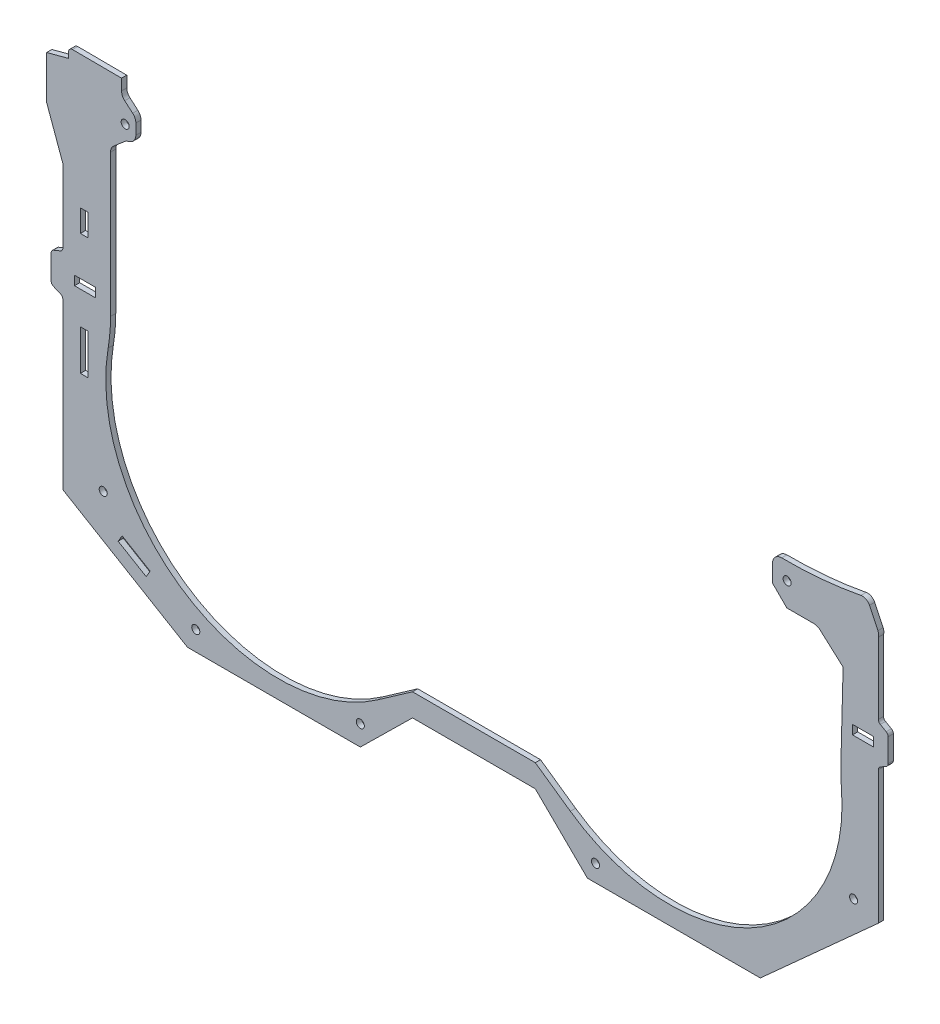
SolidWorks part; units mm, degrees
material "PPS"
ref_plane "前视基准面" through (0, 0, 0) normal (0, 0, 1) x (1, 0, 0)
ref_plane "上视基准面" through (0, 0, 0) normal (0, 1, 0) x (1, 0, 0)
ref_plane "右视基准面" through (0, 0, 0) normal (1, 0, 0) x (0, 0, -1)
sketch "草图1" plane through (0, 0, 0) normal (0, 0, 1) x (1, 0, 0)
  line L0 (-816.4831, 0) -> (39952.7477, 0) construction
  line L1 (0, 10.8762) -> (0, -592.6628) construction
  line L2 (0, 0) -> (206.9686, -284.8678) construction
  line L9 (155.1848, -135.6229) -> (109.8918, -176.4655)
  line L10 (109.8918, -176.4655) -> (43.5772, -176.4655)
  line L60 (-109.8918, -176.4655) -> (-43.5772, -176.4655)
  line L119 (-133.4625, -19.9819) -> (-139.4195, -25.1039)
  line L187 (152.75, -77.5) -> (145.75, -77.5) construction
  line L188 (152.75, -77.5) -> (152.75, -75) construction
  line L189 (145.75, -77.5) -> (145.75, -75) construction
  line L190 (152.75, -75) -> (145.75, -75) construction
  line L191 (-145.75, -75) -> (-152.75, -75) construction
  line L192 (-152.75, -75) -> (-152.75, -77.5) construction
  line L193 (-152.75, -77.5) -> (-145.75, -77.5) construction
  line L194 (-145.75, -77.5) -> (-145.75, -75) construction
  line L195 (145.25, -74.5) -> (153.25, -74.5)
  line L196 (153.25, -74.5) -> (153.25, -78)
  line L197 (153.25, -78) -> (145.25, -78)
  line L198 (145.25, -78) -> (145.25, -74.5)
  line L199 (-153.25, -78) -> (-145.25, -78)
  line L200 (-153.25, -74.5) -> (-153.25, -78)
  line L201 (-145.25, -74.5) -> (-153.25, -74.5)
  line L202 (-145.25, -78) -> (-145.25, -74.5)
  line L204 (-135.1929, 0) -> (-155.5041, 0.108)
  line L205 (-155.5041, 3.8169) -> (-155.5041, -3.6009) construction
  line L206 (-155.5041, 0.108) -> (-155.5041, -3.6009)
  line L207 (-155.5041, -3.6009) -> (-163.9299, -5.8429)
  line L208 (-155.5041, -3.6009) -> (-170.0041, -7.4592) construction
  line L209 (-163.9299, -5.8429) -> (-163.9299, -22.4613)
  line L210 (-163.9299, -22.4613) -> (-157.7253, -39.5836)
  line L211 (-157.7253, -39.5836) -> (-157.7253, -148.0115)
  line L212 (-157.7253, -148.0115) -> (-109.8918, -176.4655)
  line L215 (114.5778, -32.685) -> (114.5778, -42.9165)
  line L216 (120.0778, -48.4165) -> (131.782, -48.4165)
  line L217 (131.782, -48.4165) -> (141.6604, -57.2625)
  line L219 (151.7709, -31.6811) -> (155.0114, -38.4796)
  line L220 (155.1848, -40.6053) -> (155.1848, -135.6229)
  line L221 (120.1823, -39.335) -> (149.4323, -39.335) construction
  line L222 (96.3769, -48.4165) -> (142.5788, -48.4165) construction
  line L223 (75, -103.2286) -> (164.6276, -103.2286) construction
  line L224 (75, -103.2286) -> (37.0006, -157.4975) construction
  line L226 (37.0006, -157.4975) -> (23.5599, -148.0862)
  line L227 (23.5599, -148.0862) -> (-23.5599, -148.0862)
  line L228 (23.5599, -156.7643) -> (-23.5599, -156.7643)
  line L229 (23.5599, -156.7643) -> (43.5772, -176.4655)
  line L230 (-37.0006, -157.4975) -> (-23.5599, -148.0862)
  line L231 (-23.5599, -156.7643) -> (-43.5772, -176.4655)
  line L233 (114.5778, -42.9165) -> (120.0778, -48.4165)
  line L234 (75, -103.2286) -> (140.6832, -94.5813) construction
  line L235 (141.6604, -57.2625) -> (140.6832, -94.5813)
  line L236 (140.6832, -94.5813) -> (140.6832, -61.0285) construction
  line L238 (-139.4195, -87.7629) -> (-75, -103.2286) construction
  line L239 (-75, -103.2286) -> (-141.25, -103.2286) construction
  line L240 (-139.4195, -25.1039) -> (-139.4195, -87.7629)
  line L241 (-135.1929, 0) -> (-135.1929, -5.85)
  line L242 (-135.1929, -5.85) -> (-129.7197, -10.5767)
  line L243 (-129.7197, -10.5767) -> (-129.7197, -18.7984)
  line L244 (-129.7197, -18.7984) -> (-133.4625, -19.9819)
  circle A76 centre (75, -103.2286) radius 66.25 construction
  circle A78 centre (-133.8062, -14.6009) radius 1.55
  arc A79 (155.0114, -38.4796) -> (155.1848, -40.6053) centre (152.3033, -39.7704) cw
  circle A80 centre (-75, -103.2286) radius 66.25 construction
  arc A81 (148.5011, -30.0249) -> (151.7709, -31.6811) centre (149.0628, -32.9719) cw
  arc A82 (153.902, -42.309) -> (155.0114, -38.4796) centre (152.3033, -39.7704) ccw construction
  arc A83 (148.5011, -30.0249) -> (114.5778, -32.685) centre (119.5082, 122.0773) cw
  arc A84 (97.7907, -31.2329) -> (148.5011, -30.0249) centre (119.5082, 122.0773) ccw construction
  circle A85 centre (149.4323, -39.335) radius 1.55 construction
  circle A86 centre (120.1823, -39.335) radius 1.55
  arc A87 (37.0006, -157.4975) -> (141.25, -103.2286) centre (75, -103.2286) ccw
  arc A88 (-37.0006, -157.4975) -> (-141.25, -103.2286) centre (-75, -103.2286) cw
  arc A89 (140.6832, -94.5813) -> (141.25, -103.2286) centre (75, -103.2286) cw
  arc A91 (-141.25, -103.2286) -> (-139.4195, -87.7629) centre (-75, -103.2286) cw
  point P10 (149.25, -75)
  point P29 (0, -148.0862)
  point P38 (153.25, -76.25)
  point P92 (0, -156.7643)
  dimension "D1" = 36
  dimension "D2" = 75
  dimension "D3" = 132.5
  dimension "D6" = 75
  dimension "D7" = 149.25
  dimension "D15" = 125
  dimension "D14" = 3.1
  dimension "D4" = 2.5
  dimension "D5" = 7
  dimension "D8" = 7
  dimension "D9" = 0.5
  dimension "D10" = 0.5
  dimension "D11" = 0.5
  dimension "D12" = 0.5
  dimension "D13" = 29.25
  dimension "D16" = 7.5
  dimension "D17" = 1.5
  dimension "D18" = 13.5
extrude "凸台-拉伸1" add sketch "草图1" along normal blind 2
sketch "草图2" plane through (0, 0, 0) normal (0, 0, 1) x (1, 0, 0)
  line L0 (155.1848, -68.75) -> (158.9348, -70.9151)
  line L1 (155.1848, -135.6229) -> (155.1848, -40.6053) construction
  line L2 (158.9348, -70.9151) -> (158.9348, -81.5849)
  line L3 (158.9348, -81.5849) -> (155.1848, -83.75)
  line L4 (155.1848, -83.75) -> (155.1848, -68.75)
  line L5 (153.25, -76.25) -> (184.2947, -76.25) construction
  line L6 (153.25, -78) -> (153.25, -74.5) construction
  line L7 (-153.25, -76.25) -> (-171.2105, -76.25) construction
  line L8 (-153.25, -74.5) -> (-153.25, -78) construction
  line L9 (-157.7253, -68.75) -> (-157.7253, -83.75)
  line L10 (-157.7253, -39.5836) -> (-157.7253, -148.0115) construction
  line L11 (-157.7253, -83.75) -> (-162.2253, -81.886)
  line L12 (-162.2253, -81.886) -> (-162.2253, -70.614)
  line L13 (-162.2253, -70.614) -> (-157.7253, -68.75)
  dimension "D1" = 3.75
  dimension "D2" = 7.5
  dimension "D3" = 60
  dimension "D4" = 67.5
  dimension "D5" = 4.5
extrude "凸台-拉伸2" add sketch "草图2" against normal up to surface from surface up to face at (-132.2562, -14.6009, 0) starting at face at (149.25, -76.25, 2)
fillet "圆角1" radius 66.25 2 edges at (-139.4195, -87.7629, 1) (140.6832, -94.5813, 1)
fillet "圆角4" radius 1.5 9 edges at (155.1848, -68.75, 1) (158.9348, -70.9151, 1) (155.1848, -83.75, 1) (158.9348, -81.5849, 1) (-155.5041, 0.108, 1) (-157.7253, -68.75, 1) (-162.2253, -70.614, 1) (-162.2253, -81.886, 1) (-157.7253, -83.75, 1)
sketch "板状设备接口" plane through (0, 0, 2) normal (0, 0, 1) x (1, 0, 0)
  line L0 (-151, -90.5) -> (-148, -90.5)
  line L1 (-148, -90.5) -> (-148, -106)
  line L2 (-148, -106) -> (-151, -106)
  line L3 (-151, -106) -> (-151, -90.5)
  line L4 (-148, -77.5) -> (-148, -75) construction
  line L5 (-151, -77.5) -> (-151, -75) construction
  line L6 (-151, -51) -> (-148, -51)
  line L7 (-148, -51) -> (-148, -59.5)
  line L8 (-148, -59.5) -> (-151, -59.5)
  line L9 (-151, -59.5) -> (-151, -51)
  line L10 (-145.25, -74.5) -> (-153.25, -74.5) construction
  line L11 (-153.25, -78) -> (-145.25, -78) construction
  line L12 (-134.9623, -151.9529) -> (-124.2193, -158.3434)
  line L13 (-124.2193, -158.3434) -> (-125.753, -160.9217)
  line L14 (-125.753, -160.9217) -> (-136.496, -154.5312)
  line L15 (-136.496, -154.5312) -> (-134.9623, -151.9529)
  line L21 (-157.7253, -148.0115) -> (-109.8918, -176.4655) construction
  line L22 (-131.1245, -157.7265) -> (-133.8085, -162.2385) construction
  dimension "D1" = 15
  dimension "D2" = 8.5
  dimension "D3" = 12.5
  dimension "D4" = 15.5
  dimension "D5" = 5.25
  dimension "D6" = 12.5
  dimension "D7" = 3
extrude "设备接口" cut sketch "板状设备接口" against normal through all
sketch "草图4" plane through (0, 0, 0) normal (0, 0, 1) x (1, 0, 0)
  line L0 (-157.7253, -84.7523) -> (-157.7253, -148.0115) construction
  line L1 (-109.8918, -176.4655) -> (-43.5772, -176.4655) construction
  line L2 (155.1848, -135.6229) -> (155.1848, -84.616) construction
  line L3 (-43.5772, -168.7155) -> (-43.5772, -176.4655) construction
  line L4 (43.5772, -176.4655) -> (109.8918, -176.4655) construction
  circle A0 centre (-142.2253, -140.8215) radius 1.55
  circle A1 centre (-43.5772, -168.7155) radius 1.55
  circle A2 centre (-106.713, -168.9655) radius 1.55
  circle A3 centre (46.656, -169.9655) radius 1.55
  circle A4 centre (145.6848, -132.301) radius 1.55
  dimension "D5" = 3.1
  dimension "D1" = 15.5
  dimension "D2" = 7.5
  dimension "D3" = 7.75
  dimension "D4" = 9.5
  dimension "D6" = 6.5
extrude "切除-拉伸3" cut sketch "草图4" along normal through all
fillet "圆角5" radius 3.5 7 edges at (131.782, -48.4165, 1) (114.5778, -32.685, 1) (-139.4195, -25.1039, 1) (-129.7197, -10.5767, 1) (-135.1929, -5.85, 1) (-133.4625, -19.9819, 1) (-129.7197, -18.7984, 1)
